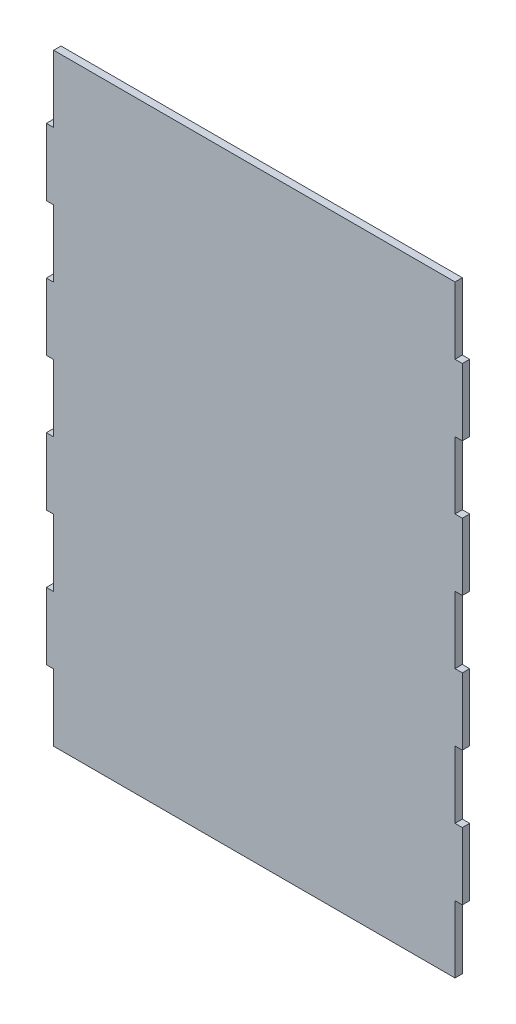
SolidWorks part; units mm, degrees
ref_plane "Ön Düzlem" through (0, 0, 0) normal (0, 0, 1) x (1, 0, 0)
ref_plane "Üst Düzlem" through (0, 0, 0) normal (0, 1, 0) x (1, 0, 0)
ref_plane "Sağ Düzlem" through (0, 0, 0) normal (1, 0, 0) x (0, 0, -1)
sketch "Sketch1" plane through (0, 0, 0) normal (0, 0, 1) x (1, 0, 0)
  line L0 (46.02, -108.65) -> (74, -108.65)
  line L3 (74, 113.65) -> (-74, 113.65)
  line L5 (73.3256, -108.65) -> (-74, 109.6493) construction
  line L6 (74, 109.6493) -> (-73.3256, -108.65) construction
  line L7 (-74, -108.65) -> (-46.02, -108.65)
  line L9 (-74, -108.65) -> (-74, -83.95)
  line L11 (74, -108.65) -> (74, -83.95)
  line L13 (-74, -59.25) -> (-74, -34.55)
  line L15 (-74, -9.85) -> (-74, 14.85)
  line L16 (-76.7, 14.85) -> (-76.7, 39.55)
  line L17 (-74, 39.55) -> (-74, 64.25)
  line L18 (-76.7, -34.55) -> (-76.7, -9.85)
  line L19 (-74, 88.95) -> (-74, 113.65)
  line L20 (76.7, -34.55) -> (76.7, -9.85)
  line L21 (74, -59.25) -> (74, -34.55)
  line L22 (76.7, 14.85) -> (76.7, 39.55)
  line L23 (74, -9.85) -> (74, 14.85)
  line L24 (76.7, 64.25) -> (76.7, 88.95)
  line L25 (74, 39.55) -> (74, 64.25)
  line L27 (74, 88.95) -> (74, 113.65)
  line L28 (-74, 88.95) -> (-76.7, 88.95)
  line L29 (-74, 64.25) -> (-76.7, 64.25)
  line L30 (-74, 39.55) -> (-76.7, 39.55)
  line L31 (-74, 14.85) -> (-76.7, 14.85)
  line L32 (-74, -9.85) -> (-76.7, -9.85)
  line L33 (-74, -34.55) -> (-76.7, -34.55)
  line L34 (-74, -83.95) -> (-76.7, -83.95)
  line L35 (74, -83.95) -> (76.7, -83.95)
  line L36 (74, 88.95) -> (76.7, 88.95)
  line L37 (74, 64.25) -> (76.7, 64.25)
  line L38 (74, 39.55) -> (76.7, 39.55)
  line L39 (74, 14.85) -> (76.7, 14.85)
  line L40 (74, -9.85) -> (76.7, -9.85)
  line L41 (74, -34.55) -> (76.7, -34.55)
  line L42 (74, -59.25) -> (76.7, -59.25)
  line L43 (-76.7, 64.25) -> (-76.7, 88.95)
  line L44 (-76.7, -83.95) -> (-76.7, -61.75)
  line L45 (76.7, -83.95) -> (76.7, -59.25)
  line L46 (-74, -59.25) -> (-76.7, -59.25)
  line L48 (-76.7, -61.75) -> (-76.7, -59.25)
  line L53 (-46.02, -108.65) -> (46.02, -108.65)
  point P0 (0, 0)
extrude "Boss-Extrude2" add sketch "Sketch1" along normal blind 2.7
